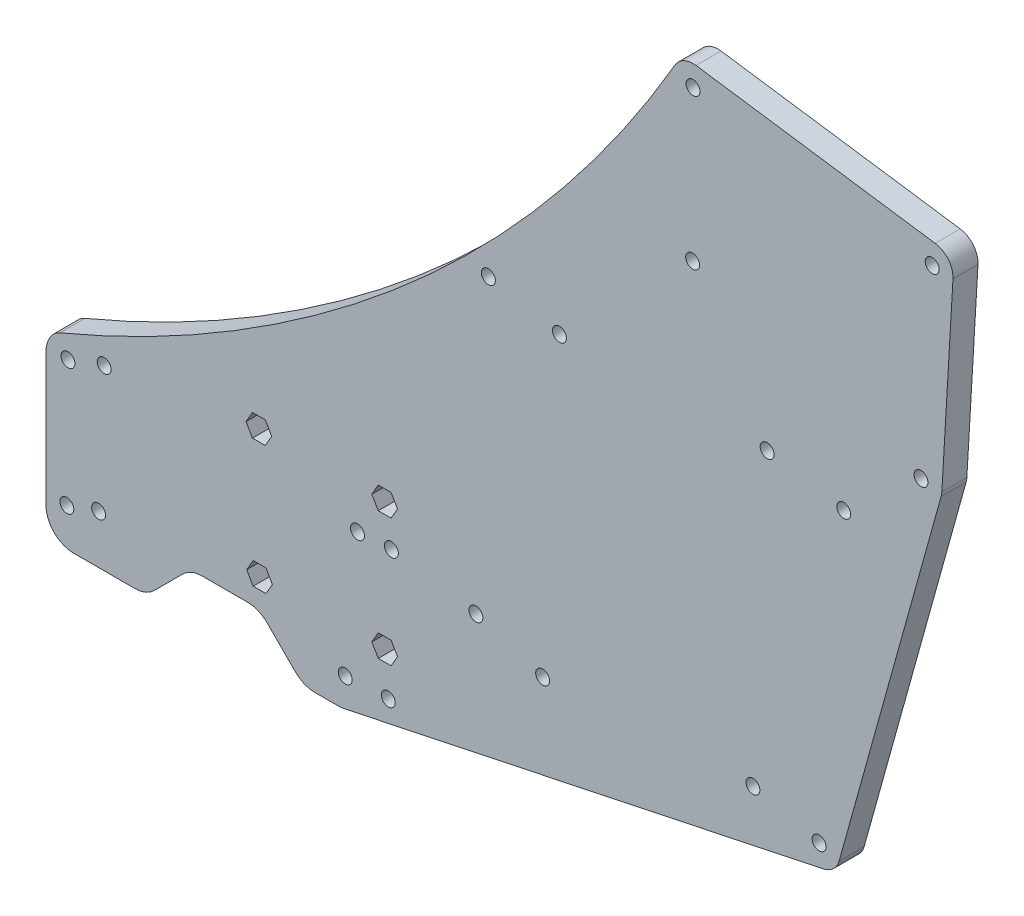
SolidWorks part; units mm, degrees
ref_plane "Front Plane" through (0, 0, 0) normal (0, 0, 1) x (1, 0, 0)
ref_plane "Top Plane" through (0, 0, 0) normal (0, 1, 0) x (1, 0, 0)
ref_plane "Right Plane" through (0, 0, 0) normal (1, 0, 0) x (0, 0, -1)
sketch "Model" plane through (0, 0, 0) normal (0, 0, 1) x (1, 0, 0)
  line L0 (-211.7059, 139.5585) -> (211.7058, 139.5585)
  line L1 (211.7058, 139.5585) -> (122.9838, -139.5584)
  line L2 (122.9838, -139.5584) -> (-211.7059, -139.5584)
  line L3 (-211.7059, -139.5584) -> (-211.7059, 139.5585)
  line L4 (-183.9889, -135.0098) -> (-175.7383, -135.0098)
  line L5 (-175.7383, -135.0098) -> (-175.7383, -139.5584)
  line L6 (-175.7383, -139.5584) -> (-183.9889, -139.5584)
  line L7 (-183.9889, -139.5584) -> (-183.9889, -135.0098)
  line L8 (5.1137, -131.3253) -> (16.7271, -131.3253)
  line L9 (16.7271, -131.3253) -> (16.7271, -139.5584)
  line L10 (16.7271, -139.5584) -> (5.1137, -139.5584)
  line L11 (5.1137, -139.5584) -> (5.1137, -131.3253)
  line L12 (-120.7856, -123.5542) -> (-97.2926, -123.5542)
  line L13 (-97.2926, -123.5542) -> (-97.2926, -126.7942)
  line L14 (-97.2926, -126.7942) -> (-120.7856, -126.7942)
  line L15 (-120.7856, -126.7942) -> (-120.7856, -123.5542)
  line L16 (-130.4136, -13.1631) -> (-127.7548, -13.1631)
  line L17 (-127.7548, -13.1631) -> (-127.7548, -110.9397)
  line L18 (-127.7548, -110.9397) -> (-130.4136, -110.9397)
  line L19 (-130.4136, -110.9397) -> (-130.4136, -13.1631)
  spline S0 degree 3 poles (121.2808, 104.4697) (121.2808, 103.8066) (121.0175, 103.1708) (120.5486, 102.7019) knots 0 0 0 0 1 1 1 1
  spline S1 degree 3 poles (120.5486, 102.7019) (120.0798, 102.2331) (119.4439, 101.9697) (118.7809, 101.9697) knots 0 0 0 0 1 1 1 1
  spline S2 degree 3 poles (118.7809, 101.9697) (117.4002, 101.9697) (116.2809, 103.089) (116.2809, 104.4697) knots 0 0 0 0 1 1 1 1
  spline S3 degree 3 poles (116.2809, 104.4697) (116.2809, 105.8504) (117.4002, 106.9696) (118.7809, 106.9696) knots 0 0 0 0 1 1 1 1
  spline S4 degree 3 poles (118.7809, 106.9696) (119.4439, 106.9696) (120.0798, 106.7062) (120.5486, 106.2374) knots 0 0 0 0 1 1 1 1
  spline S5 degree 3 poles (120.5486, 106.2374) (121.0175, 105.7686) (121.2808, 105.1327) (121.2808, 104.4697) knots 0 0 0 0 1 1 1 1
  spline S6 degree 3 poles (117.2766, 36.0936) (117.2766, 34.7129) (116.1574, 33.5937) (114.7767, 33.5937) knots 0 0 0 0 1 1 1 1
  spline S7 degree 3 poles (114.7767, 33.5937) (113.396, 33.5937) (112.2767, 34.7129) (112.2767, 36.0936) knots 0 0 0 0 1 1 1 1
  spline S8 degree 3 poles (112.2767, 36.0936) (112.2767, 37.4743) (113.396, 38.5936) (114.7767, 38.5936) knots 0 0 0 0 1 1 1 1
  spline S9 degree 3 poles (114.7767, 38.5936) (116.1574, 38.5936) (117.2766, 37.4743) (117.2766, 36.0936) knots 0 0 0 0 1 1 1 1
  spline S10 degree 3 poles (61.9275, 17.0977) (61.9275, 15.717) (60.8082, 14.5977) (59.4275, 14.5977) knots 0 0 0 0 1 1 1 1
  spline S11 degree 3 poles (59.4275, 14.5977) (58.0468, 14.5977) (56.9275, 15.717) (56.9275, 17.0977) knots 0 0 0 0 1 1 1 1
  spline S12 degree 3 poles (56.9275, 17.0977) (56.9275, 18.4784) (58.0468, 19.5976) (59.4275, 19.5976) knots 0 0 0 0 1 1 1 1
  spline S13 degree 3 poles (59.4275, 19.5976) (60.8082, 19.5976) (61.9275, 18.4784) (61.9275, 17.0977) knots 0 0 0 0 1 1 1 1
  spline S14 degree 3 poles (35.1266, 62.7496) (35.1266, 61.3689) (34.0074, 60.2496) (32.6267, 60.2496) knots 0 0 0 0 1 1 1 1
  spline S15 degree 3 poles (32.6267, 60.2496) (31.246, 60.2496) (30.1267, 61.3689) (30.1267, 62.7496) knots 0 0 0 0 1 1 1 1
  spline S16 degree 3 poles (30.1267, 62.7496) (30.1267, 64.1303) (31.246, 65.2496) (32.6267, 65.2496) knots 0 0 0 0 1 1 1 1
  spline S17 degree 3 poles (32.6267, 65.2496) (34.0074, 65.2496) (35.1266, 64.1303) (35.1266, 62.7496) knots 0 0 0 0 1 1 1 1
  spline S18 degree 3 poles (35.2798, 116.8664) (35.2798, 115.4857) (34.1605, 114.3664) (32.7798, 114.3664) knots 0 0 0 0 1 1 1 1
  spline S19 degree 3 poles (32.7798, 114.3664) (31.3991, 114.3664) (30.2798, 115.4857) (30.2798, 116.8664) knots 0 0 0 0 1 1 1 1
  spline S20 degree 3 poles (30.2798, 116.8664) (30.2798, 117.5294) (30.5432, 118.1653) (31.0121, 118.6341) knots 0 0 0 0 1 1 1 1
  spline S21 degree 3 poles (31.0121, 118.6341) (31.4809, 119.103) (32.1168, 119.3664) (32.7798, 119.3664) knots 0 0 0 0 1 1 1 1
  spline S22 degree 3 poles (32.7798, 119.3664) (33.4428, 119.3664) (34.0787, 119.103) (34.5475, 118.6341) knots 0 0 0 0 1 1 1 1
  spline S23 degree 3 poles (34.5475, 118.6341) (35.0164, 118.1653) (35.2798, 117.5294) (35.2798, 116.8664) knots 0 0 0 0 1 1 1 1
  spline S24 degree 3 poles (56.804, -89.9943) (56.804, -91.375) (55.6847, -92.4943) (54.304, -92.4943) knots 0 0 0 0 1 1 1 1
  spline S25 degree 3 poles (54.304, -92.4943) (52.9233, -92.4943) (51.804, -91.375) (51.804, -89.9943) knots 0 0 0 0 1 1 1 1
  spline S26 degree 3 poles (51.804, -89.9943) (51.804, -88.6136) (52.9233, -87.4943) (54.304, -87.4943) knots 0 0 0 0 1 1 1 1
  spline S27 degree 3 poles (54.304, -87.4943) (55.6847, -87.4943) (56.804, -88.6136) (56.804, -89.9943) knots 0 0 0 0 1 1 1 1
  spline S28 degree 3 poles (80.6115, -95.7304) (80.6115, -97.1111) (79.4922, -98.2304) (78.1115, -98.2304) knots 0 0 0 0 1 1 1 1
  spline S29 degree 3 poles (78.1115, -98.2304) (76.7308, -98.2304) (75.6115, -97.1111) (75.6115, -95.7304) knots 0 0 0 0 1 1 1 1
  spline S30 degree 3 poles (75.6115, -95.7304) (75.6115, -94.3497) (76.7308, -93.2304) (78.1115, -93.2304) knots 0 0 0 0 1 1 1 1
  spline S31 degree 3 poles (78.1115, -93.2304) (79.4922, -93.2304) (80.6115, -94.3497) (80.6115, -95.7304) knots 0 0 0 0 1 1 1 1
  spline S32 degree 3 poles (-189.541, -80.3042) (-189.541, -81.6849) (-190.6603, -82.8042) (-192.041, -82.8042) knots 0 0 0 0 1 1 1 1
  spline S33 degree 3 poles (-192.041, -82.8042) (-193.4217, -82.8042) (-194.5409, -81.6849) (-194.5409, -80.3042) knots 0 0 0 0 1 1 1 1
  spline S34 degree 3 poles (-194.5409, -80.3042) (-194.5409, -78.9235) (-193.4217, -77.8043) (-192.041, -77.8043) knots 0 0 0 0 1 1 1 1
  spline S35 degree 3 poles (-192.041, -77.8043) (-190.6603, -77.8043) (-189.541, -78.9235) (-189.541, -80.3042) knots 0 0 0 0 1 1 1 1
  spline S36 degree 3 poles (-85.4284, -81.8636) (-85.4284, -82.5266) (-85.6918, -83.1625) (-86.1606, -83.6313) knots 0 0 0 0 1 1 1 1
  spline S37 degree 3 poles (-86.1606, -83.6313) (-86.6295, -84.1001) (-87.2654, -84.3635) (-87.9284, -84.3635) knots 0 0 0 0 1 1 1 1
  spline S38 degree 3 poles (-87.9284, -84.3635) (-88.5914, -84.3635) (-89.2273, -84.1001) (-89.6961, -83.6313) knots 0 0 0 0 1 1 1 1
  spline S39 degree 3 poles (-89.6961, -83.6313) (-90.165, -83.1625) (-90.4284, -82.5266) (-90.4284, -81.8636) knots 0 0 0 0 1 1 1 1
  spline S40 degree 3 poles (-90.4284, -81.8636) (-90.4284, -80.4829) (-89.3091, -79.3636) (-87.9284, -79.3636) knots 0 0 0 0 1 1 1 1
  spline S41 degree 3 poles (-87.9284, -79.3636) (-86.5477, -79.3636) (-85.4284, -80.4829) (-85.4284, -81.8636) knots 0 0 0 0 1 1 1 1
  spline S42 degree 3 poles (-73.2184, -81.251) (-73.2184, -82.6317) (-74.3377, -83.7509) (-75.7183, -83.7509) knots 0 0 0 0 1 1 1 1
  spline S43 degree 3 poles (-75.7183, -83.7509) (-76.3814, -83.7509) (-77.0173, -83.4875) (-77.4861, -83.0187) knots 0 0 0 0 1 1 1 1
  spline S44 degree 3 poles (-77.4861, -83.0187) (-77.9549, -82.5499) (-78.2183, -81.914) (-78.2183, -81.251) knots 0 0 0 0 1 1 1 1
  spline S45 degree 3 poles (-78.2183, -81.251) (-78.2183, -80.5879) (-77.9549, -79.9521) (-77.4861, -79.4832) knots 0 0 0 0 1 1 1 1
  spline S46 degree 3 poles (-77.4861, -79.4832) (-77.0173, -79.0144) (-76.3814, -78.751) (-75.7183, -78.751) knots 0 0 0 0 1 1 1 1
  spline S47 degree 3 poles (-75.7183, -78.751) (-74.3377, -78.751) (-73.2184, -79.8703) (-73.2184, -81.251) knots 0 0 0 0 1 1 1 1
  spline S48 degree 3 poles (-42.8255, -86.1238) (-42.8255, -86.7869) (-43.0889, -87.4228) (-43.5578, -87.8916) knots 0 0 0 0 1 1 1 1
  spline S49 degree 3 poles (-43.5578, -87.8916) (-44.0266, -88.3604) (-44.6625, -88.6238) (-45.3255, -88.6238) knots 0 0 0 0 1 1 1 1
  spline S50 degree 3 poles (-45.3255, -88.6238) (-45.9885, -88.6238) (-46.6244, -88.3604) (-47.0932, -87.8916) knots 0 0 0 0 1 1 1 1
  spline S51 degree 3 poles (-47.0932, -87.8916) (-47.5621, -87.4228) (-47.8255, -86.7869) (-47.8255, -86.1238) knots 0 0 0 0 1 1 1 1
  spline S52 degree 3 poles (-47.8255, -86.1238) (-47.8255, -84.7432) (-46.7062, -83.6239) (-45.3255, -83.6239) knots 0 0 0 0 1 1 1 1
  spline S53 degree 3 poles (-45.3255, -83.6239) (-43.9448, -83.6239) (-42.8255, -84.7432) (-42.8255, -86.1238) knots 0 0 0 0 1 1 1 1
  spline S54 degree 3 poles (-18.8231, -93.7812) (-18.8231, -95.1619) (-19.9424, -96.2812) (-21.3231, -96.2812) knots 0 0 0 0 1 1 1 1
  spline S55 degree 3 poles (-21.3231, -96.2812) (-22.7038, -96.2812) (-23.823, -95.1619) (-23.823, -93.7812) knots 0 0 0 0 1 1 1 1
  spline S56 degree 3 poles (-23.823, -93.7812) (-23.823, -92.4005) (-22.7038, -91.2813) (-21.3231, -91.2813) knots 0 0 0 0 1 1 1 1
  spline S57 degree 3 poles (-21.3231, -91.2813) (-19.9424, -91.2813) (-18.8231, -92.4005) (-18.8231, -93.7812) knots 0 0 0 0 1 1 1 1
  spline S58 degree 3 poles (-38.3425, 21.163) (-38.3425, 19.7824) (-39.4618, 18.6631) (-40.8425, 18.6631) knots 0 0 0 0 1 1 1 1
  spline S59 degree 3 poles (-40.8425, 18.6631) (-42.2231, 18.6631) (-43.3424, 19.7824) (-43.3424, 21.163) knots 0 0 0 0 1 1 1 1
  spline S60 degree 3 poles (-43.3424, 21.163) (-43.3424, 22.5437) (-42.2231, 23.663) (-40.8425, 23.663) knots 0 0 0 0 1 1 1 1
  spline S61 degree 3 poles (-40.8425, 23.663) (-39.4618, 23.663) (-38.3425, 22.5437) (-38.3425, 21.163) knots 0 0 0 0 1 1 1 1
  spline S62 degree 3 poles (-12.7807, 15.9839) (-12.7807, 14.6032) (-13.9, 13.4839) (-15.2807, 13.4839) knots 0 0 0 0 1 1 1 1
  spline S63 degree 3 poles (-15.2807, 13.4839) (-16.6614, 13.4839) (-17.7807, 14.6032) (-17.7807, 15.9839) knots 0 0 0 0 1 1 1 1
  spline S64 degree 3 poles (-17.7807, 15.9839) (-17.7807, 17.3646) (-16.6614, 18.4838) (-15.2807, 18.4838) knots 0 0 0 0 1 1 1 1
  spline S65 degree 3 poles (-15.2807, 18.4838) (-13.9, 18.4838) (-12.7807, 17.3646) (-12.7807, 15.9839) knots 0 0 0 0 1 1 1 1
  spline S66 degree 3 poles (-176.5282, -75.6233) (-176.5282, -76.2863) (-176.7916, -76.9222) (-177.2604, -77.391) knots 0 0 0 0 1 1 1 1
  spline S67 degree 3 poles (-177.2604, -77.391) (-177.7293, -77.8599) (-178.3651, -78.1233) (-179.0282, -78.1233) knots 0 0 0 0 1 1 1 1
  spline S68 degree 3 poles (-179.0282, -78.1233) (-179.6912, -78.1233) (-180.3271, -77.8599) (-180.7959, -77.391) knots 0 0 0 0 1 1 1 1
  spline S69 degree 3 poles (-180.7959, -77.391) (-181.2647, -76.9222) (-181.5281, -76.2863) (-181.5281, -75.6233) knots 0 0 0 0 1 1 1 1
  spline S70 degree 3 poles (-181.5281, -75.6233) (-181.5281, -74.2426) (-180.4089, -73.1233) (-179.0282, -73.1233) knots 0 0 0 0 1 1 1 1
  spline S71 degree 3 poles (-179.0282, -73.1233) (-177.6475, -73.1233) (-176.5282, -74.2426) (-176.5282, -75.6233) knots 0 0 0 0 1 1 1 1
  spline S72 degree 3 poles (-189.9448, -125.9005) (-189.9448, -127.2812) (-191.064, -128.4004) (-192.4447, -128.4004) knots 0 0 0 0 1 1 1 1
  spline S73 degree 3 poles (-192.4447, -128.4004) (-193.8254, -128.4004) (-194.9447, -127.2812) (-194.9447, -125.9005) knots 0 0 0 0 1 1 1 1
  spline S74 degree 3 poles (-194.9447, -125.9005) (-194.9447, -124.5198) (-193.8254, -123.4005) (-192.4447, -123.4005) knots 0 0 0 0 1 1 1 1
  spline S75 degree 3 poles (-192.4447, -123.4005) (-191.064, -123.4005) (-189.9448, -124.5198) (-189.9448, -125.9005) knots 0 0 0 0 1 1 1 1
  spline S76 degree 3 poles (-178.5283, -121.9882) (-178.5283, -123.3689) (-179.6475, -124.4882) (-181.0282, -124.4882) knots 0 0 0 0 1 1 1 1
  spline S77 degree 3 poles (-181.0282, -124.4882) (-181.6913, -124.4882) (-182.3271, -124.2248) (-182.796, -123.756) knots 0 0 0 0 1 1 1 1
  spline S78 degree 3 poles (-182.796, -123.756) (-183.2648, -123.2871) (-183.5282, -122.6513) (-183.5282, -121.9882) knots 0 0 0 0 1 1 1 1
  spline S79 degree 3 poles (-183.5282, -121.9882) (-183.5282, -121.3252) (-183.2648, -120.6893) (-182.796, -120.2205) knots 0 0 0 0 1 1 1 1
  spline S80 degree 3 poles (-182.796, -120.2205) (-182.3271, -119.7516) (-181.6913, -119.4882) (-181.0282, -119.4882) knots 0 0 0 0 1 1 1 1
  spline S81 degree 3 poles (-181.0282, -119.4882) (-180.3652, -119.4882) (-179.7293, -119.7516) (-179.2605, -120.2205) knots 0 0 0 0 1 1 1 1
  spline S82 degree 3 poles (-179.2605, -120.2205) (-178.7917, -120.6893) (-178.5283, -121.3252) (-178.5283, -121.9882) knots 0 0 0 0 1 1 1 1
  spline S83 degree 3 poles (-74.3322, -128.3369) (-74.3322, -129.7176) (-75.4514, -130.8369) (-76.8321, -130.8369) knots 0 0 0 0 1 1 1 1
  spline S84 degree 3 poles (-76.8321, -130.8369) (-77.4952, -130.8369) (-78.1311, -130.5735) (-78.5999, -130.1046) knots 0 0 0 0 1 1 1 1
  spline S85 degree 3 poles (-78.5999, -130.1046) (-79.0687, -129.6358) (-79.3321, -128.9999) (-79.3321, -128.3369) knots 0 0 0 0 1 1 1 1
  spline S86 degree 3 poles (-79.3321, -128.3369) (-79.3321, -127.6739) (-79.0687, -127.038) (-78.5999, -126.5692) knots 0 0 0 0 1 1 1 1
  spline S87 degree 3 poles (-78.5999, -126.5692) (-78.1311, -126.1003) (-77.4952, -125.8369) (-76.8321, -125.8369) knots 0 0 0 0 1 1 1 1
  spline S88 degree 3 poles (-76.8321, -125.8369) (-75.4514, -125.8369) (-74.3322, -126.9562) (-74.3322, -128.3369) knots 0 0 0 0 1 1 1 1
  spline S89 degree 3 poles (-89.8001, -128.9495) (-89.8001, -129.6125) (-90.0635, -130.2484) (-90.5323, -130.7172) knots 0 0 0 0 1 1 1 1
  spline S90 degree 3 poles (-90.5323, -130.7172) (-91.0012, -131.1861) (-91.637, -131.4494) (-92.3001, -131.4494) knots 0 0 0 0 1 1 1 1
  spline S91 degree 3 poles (-92.3001, -131.4494) (-93.6808, -131.4494) (-94.8, -130.3302) (-94.8, -128.9495) knots 0 0 0 0 1 1 1 1
  spline S92 degree 3 poles (-94.8, -128.9495) (-94.8, -127.5688) (-93.6808, -126.4495) (-92.3001, -126.4495) knots 0 0 0 0 1 1 1 1
  spline S93 degree 3 poles (-92.3001, -126.4495) (-91.637, -126.4495) (-91.0012, -126.7129) (-90.5323, -127.1817) knots 0 0 0 0 1 1 1 1
  spline S94 degree 3 poles (-90.5323, -127.1817) (-90.0635, -127.6506) (-89.8001, -128.2864) (-89.8001, -128.9495) knots 0 0 0 0 1 1 1 1
  spline S95 degree 3 poles (89.4662, 12.2666) (89.4662, 10.8859) (88.3469, 9.7666) (86.9662, 9.7666) knots 0 0 0 0 1 1 1 1
  spline S96 degree 3 poles (86.9662, 9.7666) (85.5855, 9.7666) (84.4663, 10.8859) (84.4663, 12.2666) knots 0 0 0 0 1 1 1 1
  spline S97 degree 3 poles (84.4663, 12.2666) (84.4663, 13.6472) (85.5855, 14.7665) (86.9662, 14.7665) knots 0 0 0 0 1 1 1 1
  spline S98 degree 3 poles (86.9662, 14.7665) (88.3469, 14.7665) (89.4662, 13.6472) (89.4662, 12.2666) knots 0 0 0 0 1 1 1 1
sketch "Sketch2" plane through (0, 0, 0) normal (0, 0, 1) x (1, 0, 0)
  line L0 (-211.7059, -139.5584) -> (122.9838, -139.5584)
  line L18 (-211.7059, -139.5584) -> (-211.7059, 139.5585)
  line L19 (-211.7059, 139.5585) -> (211.7058, 139.5585)
  line L20 (211.7058, 139.5585) -> (122.9838, -139.5584)
  circle A0 centre (-192.4447, -125.9005) radius 2.5
  circle A1 centre (-181.0282, -121.9882) radius 2.5
  circle A2 centre (-192.041, -80.3042) radius 2.5
  circle A3 centre (-179.0282, -75.6233) radius 2.5
  circle A4 centre (-92.3001, -128.9495) radius 2.5
  circle A5 centre (-76.8321, -128.3369) radius 2.5
  circle A6 centre (-87.9284, -81.8636) radius 2.5
  circle A7 centre (-75.7183, -81.251) radius 2.5
  circle A8 centre (-45.3255, -86.1239) radius 2.5
  circle A9 centre (-21.3231, -93.7812) radius 2.5
  circle A10 centre (54.304, -89.9943) radius 2.5
  circle A11 centre (78.1115, -95.7304) radius 2.5
  circle A12 centre (114.7767, 36.0936) radius 2.5
  circle A13 centre (86.9662, 12.2666) radius 2.5
  circle A14 centre (59.4275, 17.0977) radius 2.5
  circle A15 centre (-40.8425, 21.163) radius 2.5
  circle A16 centre (-15.2807, 15.9839) radius 2.5
  circle A17 centre (32.6267, 62.7496) radius 2.5
  circle A18 centre (118.7809, 104.4697) radius 2.5
  circle A19 centre (32.7798, 116.8664) radius 2.5
extrude "Boss-Extrude1" add sketch "Sketch2" along normal blind 9
sketch "Sketch3" plane through (0, 0, 9) normal (0, 0, 1) x (1, 0, 0)
  line L0 (73.706, -139.5584) -> (151.3388, 139.5585)
  line L1 (-211.7059, -139.5584) -> (122.9838, -139.5584) construction
  line L2 (-211.7059, 139.5585) -> (211.7058, 139.5585) construction
  line L3 (-199.9447, 139.5585) -> (-199.9447, -139.5584)
  line L4 (-211.7059, -87.5749) -> (47.2794, 139.5585)
  line L5 (-211.7059, -139.5584) -> (-211.7059, 139.5585) construction
  line L6 (-211.7059, 124.3664) -> (206.8768, 124.3664)
  line L7 (211.7058, 139.5585) -> (122.9838, -139.5584) construction
  line L9 (211.7058, 139.5585) -> (-211.7059, 139.5585)
  line L10 (211.7058, 139.5585) -> (211.7058, -139.5584)
  line L11 (211.7058, -139.5584) -> (-211.7059, -139.5584)
  line L12 (-211.7059, 139.5585) -> (-211.7059, -139.5584)
  circle A0 centre (114.7767, 36.0936) radius 7.5
  circle A1 centre (78.1115, -95.7304) radius 7.5
  circle A2 centre (-192.4447, -125.9005) radius 7.5
  circle A3 centre (-192.041, -80.3042) radius 7.5
  circle A4 centre (32.7798, 116.8664) radius 7.5
  circle A5 centre (114.7767, 36.0936) radius 2.5 construction
  circle A6 centre (118.7809, 104.4697) radius 7.5
  line M29 (122.9838, -139.5584) -> (211.7058, 139.5585)
  line M30 (211.7058, 139.5585) -> (-211.7059, 139.5585)
  line M31 (-211.7059, 139.5585) -> (-211.7059, -139.5584)
  line M32 (-211.7059, -139.5584) -> (122.9838, -139.5584)
  dimension "D1" = 15
extrude "Cut-Extrude1" cut sketch "Sketch3" against normal blind 10 contours L6 L4 L3 M31 | L4 L3 M31 M32 | L6 L0 M32 M29 | L6 L3 L4 | L6 L3 M31 M30 | L3 L6 L4 M30 | L4 L6 L0 M30 | L0 L6 M29 M30 | L12 L11 L10 L9
sketch "Sketch4" plane through (0, 0, 9) normal (0, 0, 1) x (1, 0, 0)
  line L5 (-163.8851, -139.5584) -> (-147.8809, -123.5542)
  line L6 (-199.9447, -139.5584) -> (73.706, -139.5584) construction
  line L7 (-147.8809, -123.5542) -> (-123.3337, -123.5542)
  line L8 (-123.3337, -123.5542) -> (-107.3295, -139.5584)
  line L9 (-107.3295, -139.5584) -> (-163.8851, -139.5584)
  line L10 (-155.883, -131.5563) -> (-115.3316, -131.5563) construction
  line L11 (-135.6073, -123.5542) -> (-135.6073, -131.5563) construction
  line L12 (-128.1309, -123.5542) -> (-73.1309, -123.5542) construction
  line L13 (-147.8809, -91.0542) -> (-123.3337, -91.0542) construction
  line L14 (-147.8809, -85.5542) -> (-147.8809, -96.5542) construction
  line L15 (-123.3337, -72.156) -> (-123.3337, -109.9525) construction
  line L16 (-135.6073, -123.5542) -> (-135.6073, -91.0542) construction
  line L17 (-147.8809, -117.5859) -> (-147.8809, -123.5542) construction
  dimension "D1" = 45
extrude "Cut-Extrude2" cut sketch "Sketch4" against normal through all
sketch "Sketch5" plane through (0, 0, 9) normal (0, 0, 1) x (1, 0, 0)
  line L0 (-120.6309, -113.5542) -> (-125.6309, -113.5542) construction
  line L1 (-120.6309, -117.5542) -> (-120.6309, -109.5542) construction
  line L3 (-123.3809, -117.5859) -> (-123.3809, -64.5226) construction
  line L4 (-75.6309, -67.5542) -> (-80.6309, -67.5542) construction
  line L5 (-75.6309, -72.0542) -> (-75.6309, -63.0542) construction
  line L6 (-80.6309, -63.0542) -> (-80.6309, -72.0542) construction
  line L7 (-78.1309, -67.5542) -> (-123.3809, -67.5542) construction
  line L8 (-78.1309, -113.5542) -> (-78.1309, -67.5542) construction
  line L9 (-123.1309, -113.5542) -> (-78.1309, -113.5542) construction
  circle A0 centre (-123.1309, -113.5542) radius 2.5
  circle A1 centre (-78.1309, -113.5542) radius 2.5
  circle A2 centre (-123.3809, -67.5542) radius 2.5
  circle A3 centre (-78.1309, -67.5542) radius 2.5
  dimension "D1" = 5
extrude "Cut-Extrude3" cut sketch "Sketch5" against normal through all
sketch "Sketch6" plane through (0, 0, 9) normal (0, 0, 1) x (1, 0, 0)
  line L0 (-199.9447, -77.2602) -> (-199.9447, -139.5584) construction
  line L1 (-194.9336, -73.3845) -> (-199.9447, -73.3845)
  line L2 (-199.9447, -139.5584) -> (147.1133, -139.5584)
  line L3 (-199.9447, -139.5584) -> (-199.9447, 124.3664)
  line L4 (-199.9447, 124.3664) -> (147.1133, 124.3664)
  line L5 (147.1133, -139.5584) -> (147.1133, 124.3664)
  line L6 (26.2967, 120.6372) -> (26.2967, 124.3664)
  line L7 (33.8498, 124.2897) -> (119.8509, 111.8929)
  line L8 (126.2681, 104.0312) -> (122.2638, 35.6552)
  line L9 (122.2638, 35.6552) -> (147.1133, 35.6552)
  line L10 (79.656, -103.0696) -> (-93.736, -139.5584)
  line L11 (79.656, -103.0696) -> (147.1133, -103.0696)
  circle A0 centre (-192.041, -80.3042) radius 7.5
  circle A1 centre (-40.8425, 21.163) radius 7.5
  circle A3 centre (114.7767, 36.0936) radius 7.5
  circle A4 centre (32.7798, 116.8664) radius 7.5
  circle A5 centre (118.7809, 104.4697) radius 7.5
  circle A6 centre (78.1115, -95.7304) radius 7.5
  circle A7 centre (-76.8321, -128.3369) radius 7.5
  circle A8 centre (-192.4447, -125.9005) radius 7.5
  circle A9 centre (-179.0282, -75.6233) radius 7.5
  arc A10 (-194.9336, -73.3845) -> (26.2967, 120.6372) centre (-373.1679, 352.9825) ccw
  line M19 (73.706, -139.5584) -> (147.1133, 124.3664)
  line M20 (147.1133, 124.3664) -> (29.9569, 124.3664)
  line M21 (29.9569, 124.3664) -> (-199.9447, -77.2602)
extrude "Cut-Extrude5" cut sketch "Sketch6" against normal blind 10 contours L1 A10 L6 M21 | L9 L5 M19 | L11 L10 L2 M19 | A6 L11 M19 | A0 L1 M21 | L6 L4 M21 | A4 L6 M21 | A4 L4 M21 | A5 L8 L9 A4 L7 M19 M20 | A3 L9 M19
fillet "Fillet1" radius 10 7 edges at (-199.9447, -77.2602, 4.5) (-163.8851, -139.5584, 4.5) (-147.8809, -123.5542, 4.5) (-123.3337, -123.5542, 4.5) (-107.3295, -139.5584, 4.5) (-93.736, -139.5584, 4.5) (-199.9447, -139.5584, 4.5)
sketch "Sketch7" plane through (0, 0, 0) normal (0, 0, 1) x (1, 0, 0)
  line L1 (-118.5121, -113.5542) -> (-120.8215, -109.5542)
  line L2 (-120.8215, -109.5542) -> (-125.4403, -109.5542)
  line L3 (-125.4403, -109.5542) -> (-127.7497, -113.5542)
  line L4 (-127.7497, -113.5542) -> (-125.4403, -117.5542)
  line L5 (-125.4403, -117.5542) -> (-120.8215, -117.5542)
  line L6 (-120.8215, -117.5542) -> (-118.5121, -113.5542)
  line L7 (-82.7497, -113.5542) -> (-80.4403, -117.5542)
  line L8 (-80.4403, -117.5542) -> (-75.8215, -117.5542)
  line L9 (-75.8215, -117.5542) -> (-73.5121, -113.5542)
  line L10 (-73.5121, -113.5542) -> (-75.8215, -109.5542)
  line L11 (-75.8215, -109.5542) -> (-80.4403, -109.5542)
  line L12 (-80.4403, -109.5542) -> (-82.7497, -113.5542)
  line L13 (-80.4403, -71.5542) -> (-75.8215, -71.5542)
  line L14 (-75.8215, -71.5542) -> (-73.5121, -67.5542)
  line L15 (-73.5121, -67.5542) -> (-75.8215, -63.5542)
  line L16 (-75.8215, -63.5542) -> (-80.4403, -63.5542)
  line L17 (-80.4403, -63.5542) -> (-82.7497, -67.5542)
  line L18 (-82.7497, -67.5542) -> (-80.4403, -71.5542)
  line L19 (-121.0715, -71.5542) -> (-118.7621, -67.5542)
  line L20 (-118.7621, -67.5542) -> (-121.0715, -63.5542)
  line L21 (-121.0715, -63.5542) -> (-125.6903, -63.5542)
  line L22 (-125.6903, -63.5542) -> (-127.9997, -67.5542)
  line L23 (-127.9997, -67.5542) -> (-125.6903, -71.5542)
  line L24 (-125.6903, -71.5542) -> (-121.0715, -71.5542)
  circle A0 centre (-123.1309, -113.5542) radius 4 construction
  circle A1 centre (-78.1309, -113.5542) radius 4 construction
  circle A2 centre (-78.1309, -67.5542) radius 4 construction
  circle A3 centre (-123.3809, -67.5542) radius 4 construction
  point P40 (0, 0)
  point P41 (-119.8524, -118.8448)
  point P42 (0, 0)
  point P43 (0, 0)
  dimension "D1" = 8
extrude "Cut-Extrude7" cut sketch "Sketch7" along normal through all
